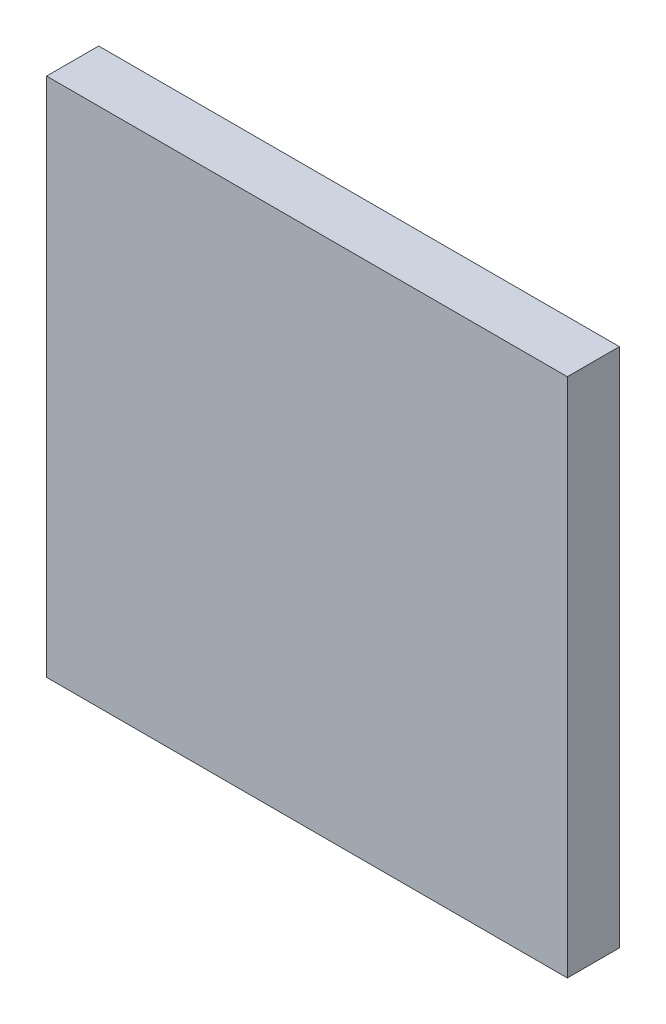
SolidWorks part; units mm, degrees
ref_plane "前视基准面" through (0, 0, 0) normal (0, 0, 1) x (1, 0, 0)
ref_plane "上视基准面" through (0, 0, 0) normal (0, 1, 0) x (1, 0, 0)
ref_plane "右视基准面" through (0, 0, 0) normal (1, 0, 0) x (0, 0, -1)
other "Configuration Table"
sketch "草图1" plane through (0, 0, 0) normal (0, 0, 1) x (1, 0, 0)
  line L1 (0, 0) -> (20000, 0)
  line L2 (0, 0) -> (0, 20000)
  line L3 (0, 20000) -> (20000, 20000)
  line L4 (20000, 0) -> (20000, 20000)
extrude "凸台-拉伸1" add sketch "草图1" along normal blind 2000
